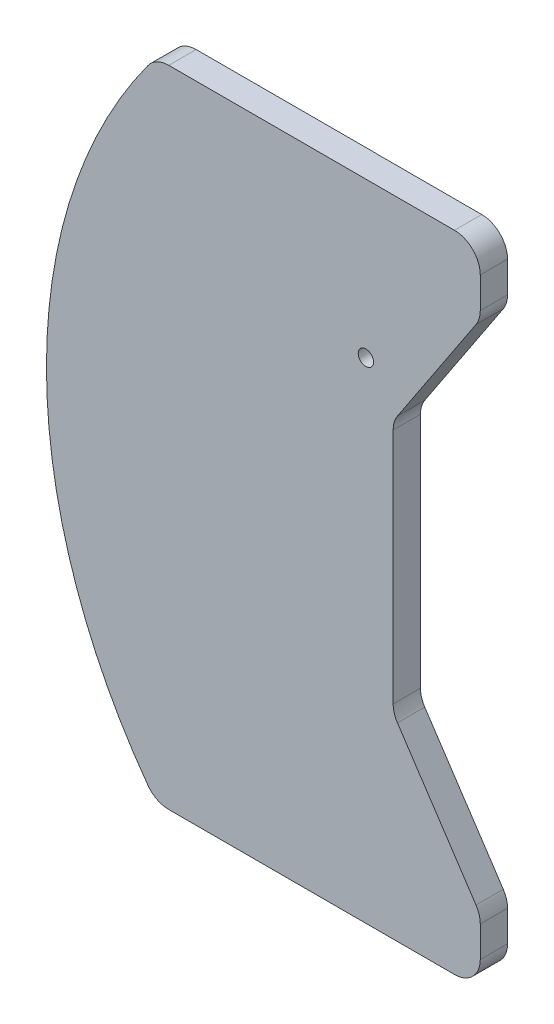
SolidWorks part; units mm, degrees
material "6061 Alloy"
ref_plane "Front Plane" through (0, 0, 0) normal (0, 0, 1) x (1, 0, 0)
ref_plane "Top Plane" through (0, 0, 0) normal (0, 1, 0) x (1, 0, 0)
ref_plane "Right Plane" through (0, 0, 0) normal (1, 0, 0) x (0, 0, -1)
sketch "Sketch1" plane through (0, 0, 0) normal (0, 0, 1) x (1, 0, 0)
  line L0 (-52.859, 37.5) -> (-15.109, 37.5)
  line L4 (-15.109, -37.5) -> (-52.859, -37.5)
  line L14 (-25.245, 14.7069) -> (-25.245, -14.7069)
  line L16 (-15.109, 37.5) -> (-15.109, 30)
  line L19 (-15.109, -37.5) -> (-15.109, -30)
  line L21 (-15.109, 30) -> (-25.245, 14.7069)
  line L26 (-15.109, -30) -> (-25.245, -14.7069)
  arc A0 (-52.859, 37.5) -> (-52.859, -37.5) centre (-3.995, 0) ccw
  circle A1 centre (-28.42, 19.5) radius 0.889
  dimension "D5" = 10.136
  dimension "D1" = 1.778
  dimension "D4" = 3.175
  dimension "D8" = 61.595
  dimension "D2" = 18
  dimension "D3" = 37.75
  dimension "D6" = 7.5
  dimension "D7" = 15.2931
extrude "Boss-Extrude1" add sketch "Sketch1" along normal blind 3.175 contours A0 region at (-41.3078, -0.016, 0)
fillet "Fillet1" radius 3 8 edges at (-15.109, -30, 1.5875) (-15.109, 30, 1.5875) (-25.245, -14.7069, 1.5875) (-25.245, 14.7069, 1.5875) (-15.109, 37.5, 1.5875) (-52.859, 37.5, 1.5875) (-52.859, -37.5, 1.5875) (-15.109, -37.5, 1.5875)
sketch "Sketch3" plane through (0, 0, 0) normal (0, 0, -1) x (-1, 0, 0)
  line L7 (18.109, -37.5) -> (51.3566, -37.5)
  line L8 (18.109, -37.5) -> (51.3566, -37.5)
  line L9 (51.3566, 37.5) -> (18.109, 37.5)
  line L10 (51.3566, 37.5) -> (18.109, 37.5)
  line L11 (25.245, 13.803) -> (25.245, -13.803)
  line L12 (47.6066, -37.5) -> (30.3545, -37.5)
  line L13 (47.6066, 37.5) -> (30.3545, 37.5)
  line L14 (25.245, 13.803) -> (25.245, -13.803)
  line L19 (24.7456, -15.4603) -> (15.6084, -29.2465)
  line L20 (15.109, -30.9039) -> (15.109, -34.5)
  line L23 (15.109, 34.5) -> (15.109, 30.9039)
  line L36 (15.6084, 29.2465) -> (24.7456, 15.4603)
  arc A4 (30.3545, -37.5) -> (30.3545, 37.5) centre (-18.5095, 0) ccw
  arc A8 (42.6123, 7.62) -> (30.3545, 37.5) centre (-18.5095, 0) ccw
  arc A11 (30.3545, -37.5) -> (42.6123, -7.62) centre (-18.5095, 0) ccw
  arc A15 (15.109, -34.5) -> (18.109, -37.5) centre (18.109, -34.5) ccw
  arc A16 (15.109, -34.5) -> (18.109, -37.5) centre (18.109, -34.5) ccw
  arc A17 (15.6084, -29.2465) -> (15.109, -30.9039) centre (18.109, -30.9039) ccw
  arc A18 (51.3566, -37.5) -> (53.7815, -36.2664) centre (51.3566, -34.5) ccw
  arc A19 (51.3566, -37.5) -> (53.7815, -36.2664) centre (51.3566, -34.5) ccw
  arc A20 (53.7815, -36.2664) -> (53.7815, 36.2664) centre (3.995, 0) ccw
  arc A21 (53.7815, 36.2664) -> (51.3566, 37.5) centre (51.3566, 34.5) ccw
  arc A23 (15.109, 30.9039) -> (15.6084, 29.2465) centre (18.109, 30.9039) ccw
  arc A29 (53.7815, -36.2664) -> (53.7815, 36.2664) centre (3.995, 0) ccw
  arc A31 (53.7815, 36.2664) -> (51.3566, 37.5) centre (51.3566, 34.5) ccw
  arc A32 (18.109, 37.5) -> (15.109, 34.5) centre (18.109, 34.5) ccw
  arc A33 (18.109, 37.5) -> (15.109, 34.5) centre (18.109, 34.5) ccw
  arc A34 (25.245, 13.803) -> (24.7456, 15.4603) centre (22.245, 13.803) ccw
  arc A35 (25.245, 13.803) -> (24.7456, 15.4603) centre (22.245, 13.803) ccw
  arc A36 (24.7456, -15.4603) -> (25.245, -13.803) centre (22.245, -13.803) ccw
  arc A37 (24.7456, -15.4603) -> (25.245, -13.803) centre (22.245, -13.803) ccw
  arc M56 (53.7815, -36.2664) -> (53.7815, 36.2664) centre (3.995, 0) ccw
  dimension "D1" = 0
extrude "Boss-Extrude3" add sketch "Sketch3" along normal blind 0.01 contours A4 M56 region at (-50.2857, 0, 0)
